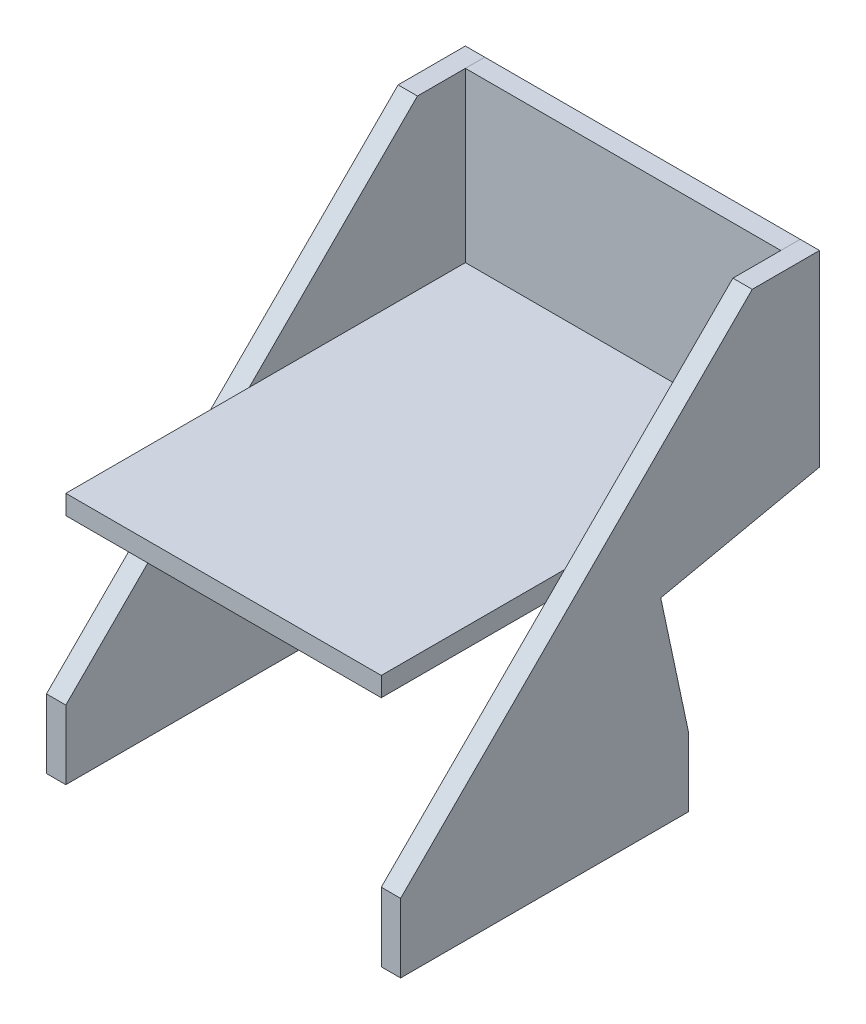
SolidWorks part; units mm, degrees
ref_plane "Front Plane" through (0, 0, 0) normal (0, 0, 1) x (1, 0, 0)
ref_plane "Top Plane" through (0, 0, 0) normal (0, 1, 0) x (1, 0, 0)
ref_plane "Right Plane" through (0, 0, 0) normal (1, 0, 0) x (0, 0, -1)
sketch "Sketch1" plane through (0, 0, 0) normal (0, 1, 0) x (1, 0, 0)
  line L1 (18.75, -23.75) -> (-18.75, -23.75)
  line L2 (18.75, -23.75) -> (18.75, 23.75)
  line L3 (18.75, 23.75) -> (-18.75, 23.75)
  line L4 (-18.75, -23.75) -> (-18.75, 23.75)
  line L5 (18.75, -23.75) -> (-18.75, 23.75) construction
  line L6 (18.75, 23.75) -> (-18.75, -23.75) construction
  point P0 (0, 0)
  dimension "D1" = 37.5
  dimension "D2" = 47.5
base flange "Base-Flange1" sketch "Sketch1" thickness 2.3 reverse thickness direction no parameters "D1"=0.7366
sketch "Sketch9" plane through (-18.75, 0, 0) normal (-1, 0, 0) x (0, 0, 1)
  line L4 (-26.05, 20) -> (23.75, 20)
  line L5 (-26.05, 20) -> (-26.05, -30)
  line L6 (-26.05, -30) -> (23.75, -30)
  line L7 (23.75, 20) -> (23.75, -30)
  dimension "D1" = 50
  dimension "D2" = 20
  dimension "D3" = 2.3
base flange "Base-Flange2" sketch "Sketch9" thickness 2.3 reverse thickness direction yes parameters "D1"=0.7366
sketch "Sketch12" plane through (0, 0, -23.75) normal (0, 0, -1) x (-1, 0, 0)
  line L1 (18.75, 20) -> (-18.75, 20)
  line L2 (18.75, 20) -> (18.75, -2.3)
  line L3 (18.75, -2.3) -> (-18.75, -2.3)
  line L4 (-18.75, 20) -> (-18.75, -2.3)
base flange "Base-Flange3" sketch "Sketch12" thickness 2.3 reverse thickness direction yes parameters "D1"=0.7366
sketch "Sketch15" plane through (18.75, 0, 0) normal (1, 0, 0) x (0, 0, -1)
  line L1 (-23.75, 20) -> (26.05, 20)
  line L2 (-23.75, 20) -> (-23.75, -30)
  line L3 (-23.75, -30) -> (26.05, -30)
  line L4 (26.05, 20) -> (26.05, -30)
base flange "Base-Flange4" sketch "Sketch15" thickness 2.3 reverse thickness direction yes parameters "D1"=0.7366
sketch "Sketch18" plane through (-21.05, 0, 0) normal (-1, 0, 0) x (0, 0, 1)
  line L0 (-18.05, 20) -> (23.75, -21.8)
  line L1 (-26.05, 20) -> (23.75, 20) construction
  line L2 (23.75, -30) -> (23.75, 20) construction
  line L3 (23.75, -21.8) -> (23.75, 20)
  line L4 (23.75, 20) -> (-18.05, 20)
  dimension "D1" = 8
  dimension "D2" = 45
extrude "Cut-Extrude1" cut sketch "Sketch18" against normal through all both and the other way through all
sketch "Sketch19" plane through (-21.05, 0, 0) normal (-1, 0, 0) x (0, 0, 1)
  line L0 (-26.05, -2.3) -> (-7.174, -6.3271)
  line L1 (-26.05, 20) -> (-26.05, -30) construction
  line L2 (-7.174, -6.3271) -> (-10.4751, -21.8)
  line L3 (-10.4751, -21.8) -> (-10.4751, -30)
  line L4 (-26.05, -30) -> (23.75, -30) construction
  line L5 (-10.4751, -30) -> (-26.05, -30)
  line L6 (-26.05, -30) -> (-26.05, -2.3)
  point P4 (0, 0)
extrude "Cut-Extrude2" cut sketch "Sketch19" against normal through all both
sketch "Bend-Lines1" [suppressed] plane through (0, 0, 0) normal (0, 1, 0) x (1, 0, 0)
sketch "Bounding-Box1" [suppressed] plane through (0, 0, 0) normal (0, 1, 0) x (1, 0, 0)
sheet metal parameters "Sheet-Metal1" thickness 2.3 parameters "D1"=0.7366
flat pattern "Flat-Pattern1" [suppressed]
sketch "Bend-Lines2" plane through (0, 0, 0) normal (0, 1, 0) x (1, 0, 0)
sketch3d "Bounding-Box2" [suppressed]
  line L0 (-18.75, 23.75, 0) -> (-18.75, -23.75, 0) construction
  line L1 (18.75, 23.75, 0) -> (18.75, -23.75, 0) construction
  line L2 (-18.75, 23.75, 0) -> (18.75, 23.75, 0) construction
  line L3 (-18.75, -23.75, 0) -> (18.75, -23.75, 0) construction
sheet metal parameters "Sheet-Metal3" thickness 2.3 parameters "D1"=0.7366
flat pattern "Flat-Pattern3"
sketch "Bend-Lines3" plane through (0, 0, 0) normal (0, 1, 0) x (1, 0, 0)
sketch3d "Bounding-Box3" [suppressed]
  line L0 (-23.75, 20, 0) -> (-23.75, -30, 0) construction
  line L1 (26.05, 20, 0) -> (26.05, -30, 0) construction
  line L2 (-23.75, 20, 0) -> (26.05, 20, 0) construction
  line L3 (-23.75, -30, 0) -> (26.05, -30, 0) construction
sheet metal parameters "Sheet-Metal4" thickness 2.3 parameters "D1"=0.7366
flat pattern "Flat-Pattern4"
sketch "Bend-Lines4" plane through (0, 0, 0) normal (0, 1, 0) x (1, 0, 0)
sketch3d "Bounding-Box4" [suppressed]
  line L0 (-18.75, -2.3, 0) -> (18.75, -2.3, 0) construction
  line L1 (-18.75, 20, 0) -> (18.75, 20, 0) construction
  line L2 (-18.75, -2.3, 0) -> (-18.75, 20, 0) construction
  line L3 (18.75, -2.3, 0) -> (18.75, 20, 0) construction
sheet metal parameters "Sheet-Metal5" thickness 2.3 parameters "D1"=0.7366
flat pattern "Flat-Pattern5"
sketch "Bend-Lines5" plane through (0, 0, 0) normal (0, 1, 0) x (1, 0, 0)
sketch "Bounding-Box5" [suppressed] plane through (0, 0, 0) normal (0, 1, 0) x (1, 0, 0)
sheet metal parameters "Sheet-Metal6" thickness 2.3 parameters "D1"=0.7366
flat pattern "Flat-Pattern3"
sketch "Bend-Lines3" plane through (0, 0, 0) normal (0, 1, 0) x (1, 0, 0)
sketch3d "Bounding-Box3" [suppressed]
  line L0 (26.05, 20, 0) -> (26.05, -30, 0) construction
  line L1 (-23.75, 20, 0) -> (-23.75, -30, 0) construction
  line L2 (26.05, 20, 0) -> (-23.75, 20, 0) construction
  line L3 (26.05, -30, 0) -> (-23.75, -30, 0) construction
sheet metal parameters "Sheet-Metal7" thickness 2.3 parameters "D1"=0.7366
flat pattern "Flat-Pattern5"
sketch "Bend-Lines5" plane through (0, 0, 0) normal (0, 1, 0) x (1, 0, 0)
sketch "Bounding-Box5" [suppressed] plane through (0, 0, 0) normal (0, 1, 0) x (1, 0, 0)
sheet metal parameters "Sheet-Metal8" thickness 2.3 parameters "D1"=0.7366
flat pattern "Flat-Pattern3"
sketch "Bend-Lines3" plane through (0, 0, 0) normal (0, 1, 0) x (1, 0, 0)
sketch3d "Bounding-Box3" [suppressed]
  line L0 (-6.6375, -47.1125, 0) -> (43.2625, 2.7875, 0) construction
  line L1 (-27.85, -25.9, 0) -> (22.05, 24, 0) construction
  line L2 (-6.6375, -47.1125, 0) -> (-27.85, -25.9, 0) construction
  line L3 (43.2625, 2.7875, 0) -> (22.05, 24, 0) construction
sheet metal parameters "Sheet-Metal9" thickness 2.3 parameters "D1"=0.7366
flat pattern "Flat-Pattern5"
sketch "Bend-Lines5" plane through (0, 0, 0) normal (0, 1, 0) x (1, 0, 0)
sketch "Bounding-Box5" [suppressed] plane through (0, 0, 0) normal (0, 1, 0) x (1, 0, 0)
